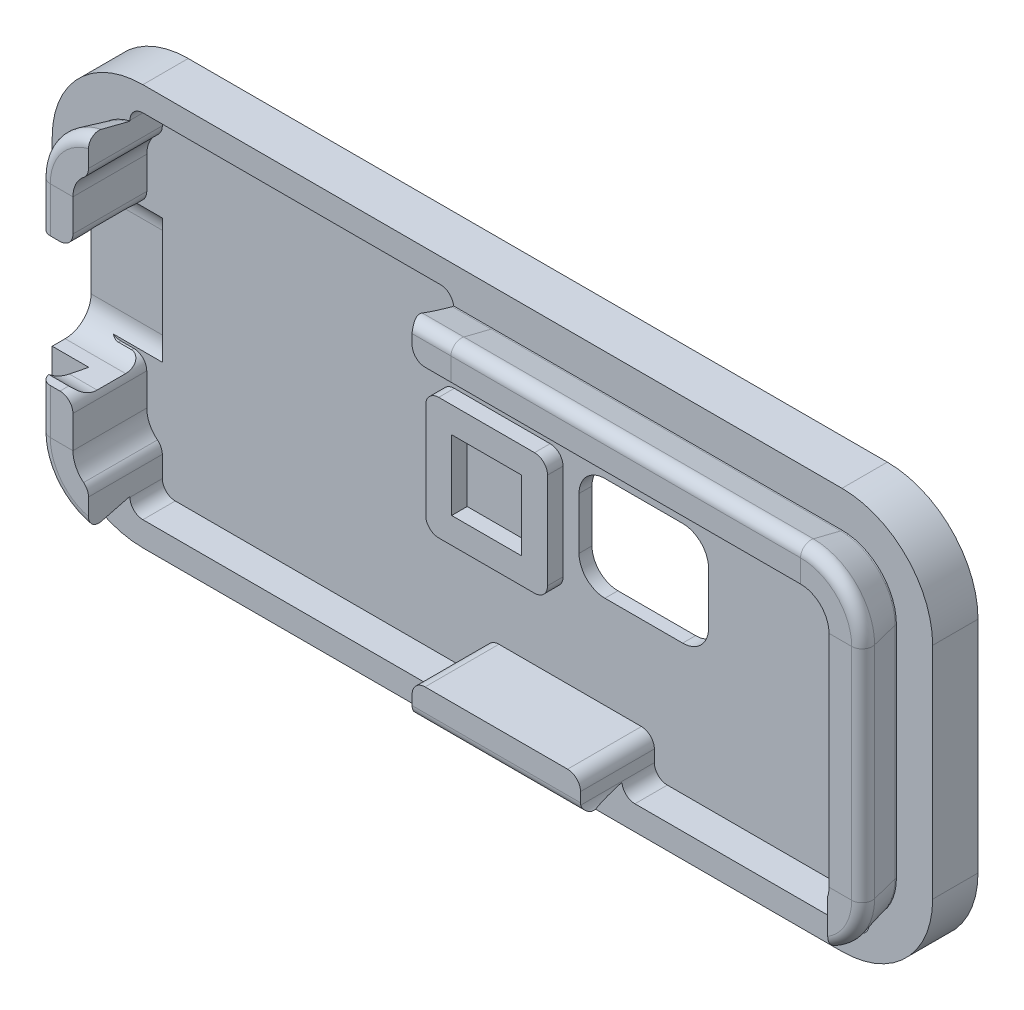
SolidWorks part; units mm, degrees
ref_plane "Ebene vorne" through (0, 0, 0) normal (0, 0, 1) x (1, 0, 0)
ref_plane "Ebene oben" through (0, 0, 0) normal (0, 1, 0) x (1, 0, 0)
ref_plane "Ebene rechts" through (0, 0, 0) normal (1, 0, 0) x (0, 0, -1)
sketch "Skizze1" plane through (0, 0, 2.3001) normal (0, 0, -1) x (-1, 0, 0)
  line L1 (-26.985, 10.685) -> (26.985, 10.685)
  line L2 (29.185, -8.485) -> (29.185, 8.485)
  line L3 (-26.985, -10.685) -> (26.985, -10.685)
  line L12 (-29.185, -8.485) -> (-29.185, 8.485)
  line L13 (-26.985, -15.485) -> (26.985, -15.485)
  line L14 (-33.985, -8.485) -> (-33.985, 8.485)
  line L15 (-26.985, 15.485) -> (26.985, 15.485)
  line L16 (33.985, -8.485) -> (33.985, 8.485)
  line L17 (-33.985, -15.485) -> (33.985, 15.485) construction
  line L18 (-33.985, 15.485) -> (33.985, -15.485) construction
  arc A0 (-33.985, -8.485) -> (-26.985, -15.485) centre (-26.985, -8.485) ccw
  arc A1 (26.985, -15.485) -> (33.985, -8.485) centre (26.985, -8.485) ccw
  arc A2 (33.985, 8.485) -> (26.985, 15.485) centre (26.985, 8.485) ccw
  arc A3 (-33.985, 8.485) -> (-26.985, 15.485) centre (-26.985, 8.485) cw
  arc A4 (29.185, 8.485) -> (26.985, 10.685) centre (26.985, 8.485) ccw
  arc A5 (26.985, -10.685) -> (29.185, -8.485) centre (26.985, -8.485) ccw
  arc A6 (-29.185, -8.485) -> (-26.985, -10.685) centre (-26.985, -8.485) ccw
  arc A7 (-29.185, 8.485) -> (-26.985, 10.685) centre (-26.985, 8.485) cw
  point P0 (0, 0)
  point P5 (0, 0)
  dimension "D5" = 7
  dimension "D1" = 67.97
  dimension "D2" = 30.97
  dimension "D3" = 4.8
extrude "Aufsatz-Linear austragen1" add sketch "Skizze1" along normal blind 3.5
sketch "Skizze2" plane through (0, 0, -1.1999) normal (0, 0, -1) x (-1, 0, 0)
  line L9 (29.185, -8.485) -> (29.185, 8.485)
  line L10 (-26.985, -10.685) -> (26.985, -10.685)
  line L11 (-29.185, 8.485) -> (-29.185, -8.485)
  line L13 (26.985, 10.685) -> (-26.985, 10.685)
  line L14 (29.185, -8.485) -> (29.185, 8.485)
  line L15 (-26.985, -10.685) -> (26.985, -10.685)
  line L20 (-29.185, 8.485) -> (-29.185, -8.485)
  line L21 (26.985, 10.685) -> (-26.985, 10.685)
  arc A20 (29.185, 8.485) -> (26.985, 10.685) centre (26.985, 8.485) ccw
  arc A21 (26.985, -10.685) -> (29.185, -8.485) centre (26.985, -8.485) ccw
  arc A22 (-29.185, -8.485) -> (-26.985, -10.685) centre (-26.985, -8.485) ccw
  arc A23 (-26.985, 10.685) -> (-29.185, 8.485) centre (-26.985, 8.485) ccw
  arc A24 (29.185, 8.485) -> (26.985, 10.685) centre (26.985, 8.485) ccw
  arc A25 (26.985, -10.685) -> (29.185, -8.485) centre (26.985, -8.485) ccw
  arc A26 (-29.185, -8.485) -> (-26.985, -10.685) centre (-26.985, -8.485) ccw
  arc A27 (-26.985, 10.685) -> (-29.185, 8.485) centre (-26.985, 8.485) ccw
  dimension "D1" = 0
extrude "Aufsatz-Linear austragen2" add sketch "Skizze2" against normal blind 1
sketch "Skizze4" plane through (0, 0, -0.1999) normal (0, 0, 1) x (1, 0, 0)
  line L2 (29.185, 8.485) -> (29.185, -8.485) construction
  line L3 (26.985, 10.685) -> (-26.985, 10.685) construction
  line L5 (14.185, 4.485) -> (4.185, 4.485)
  line L6 (14.185, 4.485) -> (14.185, -3.515)
  line L7 (14.185, -3.515) -> (4.185, -3.515)
  line L8 (4.185, 4.485) -> (4.185, -3.515)
  point P2 (-1.3995, 4.1689)
  point P3 (9.685, 4.9878)
  dimension "D1" = 15
  dimension "D2" = 10
  dimension "D3" = 8
  dimension "D4" = 6.2
extrude "Schnitt-Linear austragen1" cut sketch "Skizze4" against normal up to next
fillet "Verrundung1" radius 2 4 edges at (4.185, -3.515, -0.6999) (4.185, 4.485, -0.6999) (14.185, -3.515, -0.6999) (14.185, 4.485, -0.6999)
sketch "Skizze5" plane through (0, 0, 0) normal (1, 0, 0) x (0, 0, -1)
  line L0 (0.1999, 10.685) -> (-2.3001, 10.685) construction
  line L1 (0.1999, 10.685) -> (-2.3001, 10.685) construction
  line L2 (-2.3001, 10.685) -> (-5.5001, 10.685)
  line L3 (-5.5001, 10.685) -> (-5.5001, 13.4579)
  line L4 (-5.5001, 13.4579) -> (-2.4001, 12.685)
  line L5 (-2.4001, 12.685) -> (-2.3001, 12.685)
  line L6 (-2.3001, 12.685) -> (-2.3001, 10.685)
  dimension "D1" = 14
  dimension "D2" = 0.1
  dimension "D3" = 2
  dimension "D4" = 3.2
sketch "Skizze7" plane through (0, 0, 2.3001) normal (0, 0, 1) x (1, 0, 0)
  line L0 (-26.985, 10.685) -> (26.985, 10.685) construction
  line L1 (-26.985, 10.685) -> (26.985, 10.685)
  line L6 (-29.185, 8.485) -> (-29.185, -8.485)
  line L7 (26.985, 10.685) -> (-26.985, 10.685)
  line L8 (29.185, -8.485) -> (29.185, 8.485)
  line L9 (-26.985, -10.685) -> (26.985, -10.685)
  line L10 (-29.185, 8.485) -> (-29.185, -8.485)
  line L11 (26.985, 10.685) -> (-26.985, 10.685)
  line L12 (29.185, -8.485) -> (29.185, 8.485)
  line L13 (-26.985, -10.685) -> (26.985, -10.685)
  arc A4 (-26.985, 10.685) -> (-29.185, 8.485) centre (-26.985, 8.485) ccw
  arc A5 (29.185, 8.485) -> (26.985, 10.685) centre (26.985, 8.485) ccw
  arc A6 (26.985, -10.685) -> (29.185, -8.485) centre (26.985, -8.485) ccw
  arc A7 (-29.185, -8.485) -> (-26.985, -10.685) centre (-26.985, -8.485) ccw
  arc A8 (-26.985, 10.685) -> (-29.185, 8.485) centre (-26.985, 8.485) ccw
  arc A9 (29.185, 8.485) -> (26.985, 10.685) centre (26.985, 8.485) ccw
  arc A10 (26.985, -10.685) -> (29.185, -8.485) centre (26.985, -8.485) ccw
  arc A11 (-29.185, -8.485) -> (-26.985, -10.685) centre (-26.985, -8.485) ccw
  dimension "D1" = 0
sweep "Austragung1" add profiles "Skizze5" path "Skizze7"
fillet "Verrundung2" radius 0.8 9 edges at (30.5014, -12.0014, 5.5001) (0, -13.4579, 5.5001) (-30.5014, -12.0014, 5.5001) (-31.9579, 0, 5.5001) (-30.5014, 12.0014, 5.5001) (-13.4925, 13.4579, 5.5001) (13.4925, 13.4579, 5.5001) (30.5014, 12.0014, 5.5001) (31.9579, 0, 5.5001)
sketch "Skizze9" plane through (0, 0, 5.5001) normal (0, 0, 1) x (1, 0, 0)
  line L0 (-3, 10.1) -> (-3, -10.1)
  line L1 (-32.2, 5) -> (-28.7, 5)
  line L2 (-32.2, 5) -> (-32.2, -5)
  line L3 (-32.2, -5) -> (-28.7, -5)
  line L4 (-28.7, 5) -> (-28.7, -5)
  line L5 (29.085, -13.6) -> (10, -13.6)
  line L6 (29.085, -13.6) -> (29.085, -7.6)
  line L7 (29.085, -7.6) -> (10, -7.6)
  line L8 (10, -13.6) -> (10, -7.6)
  line L9 (-27.985, 13.6) -> (-3, 13.6)
  line L10 (-27.985, 13.6) -> (-27.985, 10.1)
  line L11 (-27.985, 10.1) -> (-3, 10.1)
  line L12 (-3, 13.6) -> (-3, 10.1)
  line L13 (-3, -10.1) -> (-27.985, -10.1)
  line L14 (-3, -10.1) -> (-3, -13.6)
  line L15 (-3, -13.6) -> (-27.985, -13.6)
  line L16 (-27.985, -10.1) -> (-27.985, -13.6)
  line L17 (-26.985, 12.434) -> (-26.985, 10.685) construction
  line L18 (29.185, -8.485) -> (29.185, 8.485) construction
  point P16 (-3, 0)
  point P17 (-28.7, 0)
  point P18 (0, 0)
  point P19 (0, 0)
  point P20 (0, 0)
  point P22 (0, 0)
  point P23 (1.6769, -16.6168)
  dimension "D1" = 27.2
  dimension "D2" = 32.2
  dimension "D3" = 3.5
  dimension "D4" = 3.5
  dimension "D5" = 10
  dimension "D6" = 1
  dimension "D7" = 3
  dimension "D8" = 0.1
  dimension "D9" = 13
  dimension "D10" = 6
extrude "Schnitt-Linear austragen2" cut sketch "Skizze9" against normal up to surface (5.7 mm away) contours L10 L9 L12 L11 | L6 L5 L8 L7 | L2 L1 L4 L3 | L14 L13 L16 L15 up to face at (9.185, 0.485, -0.1999)
fillet "Verrundung3" radius 1 24 edges at (-27.985, 13.6, 1.0501) (-27.985, 10.4446, 2.6501) (-3, 13.6, 1.0501) (-3, 10.685, 2.6501) (-3, 12.685, 2.3501) (-3, 13.1425, 2.3001) (-3, 12.9476, 3.4533) (-3, -13.6, 1.0501) (-27.985, -10.4446, 2.6501) (-27.985, -13.6, 1.0501) (-3, -10.685, 2.6501) (-3, -13.1425, 2.3001) (-3, -12.685, 2.3501) (-3, -12.9476, 3.4533) (-32.2, -5, 1.0501) (-29.185, -5, 2.6501) (-29.185, 5, 2.6501) (-32.2, 5, 1.0501) (29.085, -13.6, 1.0501) (10, -10.685, 2.6501) (10, -13.6, 1.0501) (10, -12.685, 2.3501) (10, -13.1425, 2.3001) (10, -12.9476, 3.4533)
sketch "Skizze10" plane through (-33.985, 0, 0) normal (-1, 0, 0) x (0, 0, 1)
  line L0 (2.3001, -8.485) -> (2.3001, 8.485) construction
  line L1 (3.5001, 5.5) -> (1.3001, 5.5)
  line L2 (5.5001, 3.5) -> (5.5001, -3.5)
  line L3 (3.5001, -5.5) -> (1.3001, -5.5)
  line L4 (-0.6999, 3.5) -> (-0.6999, -3.5)
  line L5 (5.5001, 5.5) -> (-0.6999, -5.5) construction
  line L6 (5.5001, -5.5) -> (-0.6999, 5.5) construction
  arc A0 (3.5001, -5.5) -> (5.5001, -3.5) centre (3.5001, -3.5) ccw
  arc A1 (1.3001, -5.5) -> (-0.6999, -3.5) centre (1.3001, -3.5) cw
  arc A2 (1.3001, 5.5) -> (-0.6999, 3.5) centre (1.3001, 3.5) ccw
  arc A3 (3.5001, 5.5) -> (5.5001, 3.5) centre (3.5001, 3.5) cw
  point P0 (2.4001, 0)
  point P17 (0, 0)
  point P19 (0.6069, 0)
  point P20 (3.6142, 0)
  dimension "D1" = 2
  dimension "D2" = 11
  dimension "D3" = 6.2
  dimension "D4" = 0.1
extrude "Schnitt-Linear austragen3" cut sketch "Skizze10" against normal blind 6
sketch "Skizze11" plane through (0, 0, -0.1999) normal (0, 0, 1) x (1, 0, 0)
  line L1 (-4.4478, -2.7) -> (0.9522, -2.7)
  line L2 (-4.4478, -2.7) -> (-4.4478, 2.7)
  line L3 (-4.4478, 2.7) -> (0.9522, 2.7)
  line L4 (0.9522, -2.7) -> (0.9522, 2.7)
  line L5 (-4.4478, -2.7) -> (0.9522, 2.7) construction
  line L6 (-4.4478, 2.7) -> (0.9522, -2.7) construction
  line L7 (-6.4478, -4.7) -> (2.9522, -4.7)
  line L8 (-6.4478, -4.7) -> (-6.4478, 4.7)
  line L9 (-6.4478, 4.7) -> (2.9522, 4.7)
  line L10 (2.9522, -4.7) -> (2.9522, 4.7)
  line L11 (-6.4478, -4.7) -> (2.9522, 4.7) construction
  line L12 (-6.4478, 4.7) -> (2.9522, -4.7) construction
  point P0 (-1.7478, 0)
  point P5 (-1.7478, 0)
  point P10 (-8.4326, -0.0533)
  point P12 (-1.7478, 0)
  point P13 (0, 0)
  dimension "D1" = 5.4
  dimension "D2" = 5.4
  dimension "D3" = 2
  dimension "D4" = 2
extrude "Aufsatz-Linear austragen3" add sketch "Skizze11" along normal blind 1.2
fillet "Verrundung4" radius 1 4 edges at (2.9522, 4.7, 0.4001) (2.9522, -4.7, 0.4001) (-6.4478, -4.7, 0.4001) (-6.4478, 4.7, 0.4001)
